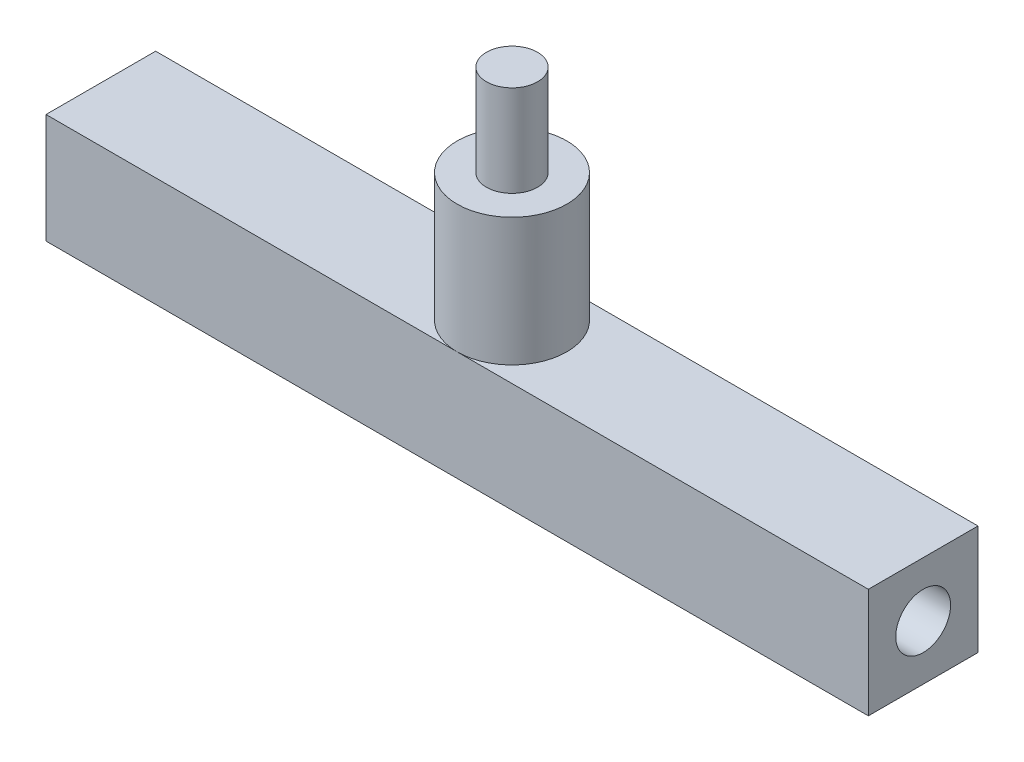
SolidWorks part; units mm, degrees
ref_plane "Front Plane" through (0, 0, 0) normal (0, 0, 1) x (1, 0, 0)
ref_plane "Top Plane" through (0, 0, 0) normal (0, 1, 0) x (1, 0, 0)
ref_plane "Right Plane" through (0, 0, 0) normal (1, 0, 0) x (0, 0, -1)
sketch "Sketch1" plane through (0, 0, 0) normal (0, 1, 0) x (1, 0, 0)
  line L1 (0, 0) -> (45, 0)
  line L2 (0, 0) -> (0, 6)
  line L3 (0, 6) -> (45, 6)
  line L4 (45, 0) -> (45, 6)
  dimension "D1" = 6
  dimension "D2" = 45
extrude "Boss-Extrude1" add sketch "Sketch1" along normal blind 6
sketch "Sketch2" plane through (0, 6, 0) normal (0, 1, 0) x (1, 0, 0)
  line L0 (0, 3) -> (45, 3) construction
  line L1 (0, 6) -> (0, 0) construction
  line L2 (45, 0) -> (45, 6) construction
  circle A0 centre (22.5, 3) radius 3
  dimension "D1" = 6
extrude "Boss-Extrude2" add sketch "Sketch2" along normal blind 7
sketch "Sketch3" plane through (0, 13, 0) normal (0, 1, 0) x (1, 0, 0)
  circle A0 centre (22.5, 3) radius 1.4
  dimension "D1" = 2.8
extrude "Boss-Extrude3" add sketch "Sketch3" along normal blind 5
hole_wizard "M3x0.5 Tapped Hole1" positions "Sketch4" profile "Sketch5" tap size "M3x0.5" standard "ANSI Metric"
sketch "Sketch4" plane through (45, 0, 0) normal (1, 0, 0) x (0, 0, -1)
  line L0 (3, 6) -> (3, 0) construction
  line L1 (0, 6) -> (6, 6) construction
  line L2 (0, 0) -> (6, 0) construction
  line L5 (6, 3) -> (0, 3) construction
  line L6 (6, 6) -> (6, 0) construction
  line L7 (0, 6) -> (0, 0) construction
  point P20 (3, 3)
sketch "Sketch5" plane through (45, 3, -3) normal (0, 1, 0) x (0, 0, -1)
  line L0 (0, 0) -> (0, 8.2511)
  line L1 (0, 8.2511) -> (1.25, 7.5)
  line L2 (1.25, 7.5) -> (1.25, 6)
  line L3 (1.25, 6) -> (1.5, 6)
  line L4 (1.5, 6) -> (1.5, 0)
  line L5 (1.5, 0) -> (0, 0)
  line L10 (0, 8.2511) -> (-1.25, 7.5) construction
  line L11 (0, -6.35) -> (0, 107.95) construction
  dimension "Tap Drill Dia." = 2.5
  dimension "Tap Drill Depth" = 7.5
  dimension "Thread Major Dia." = 3
  dimension "Thread Depth" = 6
  dimension "Drill Angle" = 118
hole_wizard "M3x0.5 Tapped Hole2" positions "Sketch6" profile "Sketch7" tap size "M3x0.5" standard "ANSI Metric"
sketch "Sketch6" plane through (0, 0, 0) normal (-1, 0, 0) x (0, 0, 1)
  point P0 (-3, 3)
sketch "Sketch7" plane through (0, 3, -3) normal (0, 1, 0) x (0, 0, 1)
  line L0 (0, 0) -> (0, 8.2511)
  line L1 (0, 8.2511) -> (1.25, 7.5)
  line L2 (1.25, 7.5) -> (1.25, 6)
  line L3 (1.25, 6) -> (1.5, 6)
  line L4 (1.5, 6) -> (1.5, 0)
  line L5 (1.5, 0) -> (0, 0)
  line L10 (0, 8.2511) -> (-1.25, 7.5) construction
  line L11 (0, -6.35) -> (0, 107.95) construction
  dimension "Tap Drill Dia." = 2.5
  dimension "Tap Drill Depth" = 7.5
  dimension "Thread Major Dia." = 3
  dimension "Thread Depth" = 6
  dimension "Drill Angle" = 118
